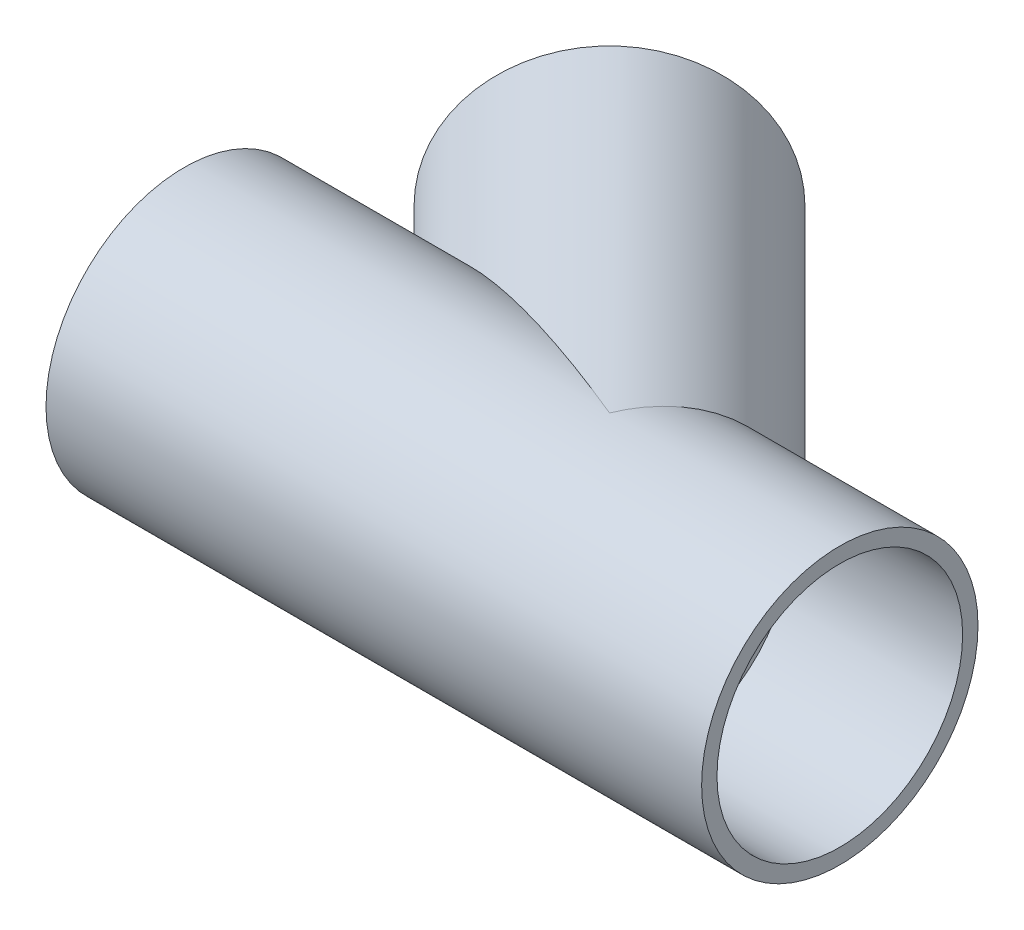
SolidWorks part; units mm, degrees
ref_plane "前视基准面" through (0, 0, 0) normal (0, 0, 1) x (1, 0, 0)
ref_plane "上视基准面" through (0, 0, 0) normal (0, 1, 0) x (1, 0, 0)
ref_plane "右视基准面" through (0, 0, 0) normal (1, 0, 0) x (0, 0, -1)
other "Configuration Table"
sketch "草图1" plane through (0, 0, 0) normal (0, 1, 0) x (1, 0, 0)
  line L0 (-41.4, 41.4) -> (0, 0)
  line L1 (0, 0) -> (30, 0)
  dimension "D3" = 30
  dimension "D1" = 135
  dimension "D2" = 41.4
sweep "扫描1" add path "草图1" circular profile diameter 36 parameters "D3"=36
sketch "草图35" plane through (30, 0, 0) normal (1, 0, 0) x (0, 0, -1)
  circle A0 centre (0, 0) radius 18
  circle A1 centre (0, 0) radius 18 construction
extrude "凸台-拉伸1" add sketch "草图35" against normal blind 85.4
ref_plane "基准面1" through (0, 0, -54.1) normal (0, 0, 1) x (1, 0, 0)
sweep "切除-扫描1" cut path "草图1<11>" circular profile diameter 27.2 parameters "D3"=27.2
sketch "草图1<11>" plane through (0, 0, 0) normal (0, 1, 0) x (1, 0, 0) same geometry as "草图1"
sketch "草图56" plane through (-55.4, 0, 0) normal (-1, 0, 0) x (0, 0, 1)
  circle A0 centre (0, 0) radius 16
  circle A1 centre (0, 0) radius 13.6
  dimension "D1" = 32
  dimension "D2" = 2.4
extrude "切除-拉伸3" cut sketch "草图56" against normal through all contours A1
sketch "草图33" plane through (30, 0, 0) normal (1, 0, 0) x (0, 0, -1)
  circle A0 centre (0, 0) radius 16
  dimension "D1" = 32
extrude "切除-拉伸1" cut sketch "草图33" against normal blind 22.2
sketch "草图34" plane through (-41.4, 0, -41.4) normal (-0.7071, 0, -0.7071) x (-0.7071, 0, 0.7071)
  circle A0 centre (0, 0) radius 16
  dimension "D1" = 32
extrude "切除-拉伸2" cut sketch "草图34" against normal blind 22.2
extrude "切除-拉伸4" cut sketch "草图56<4>" against normal blind 22.2 contours A0
sketch "草图56<4>" plane through (-55.4, 0, 0) normal (-1, 0, 0) x (0, 0, 1) same geometry as "草图56"
